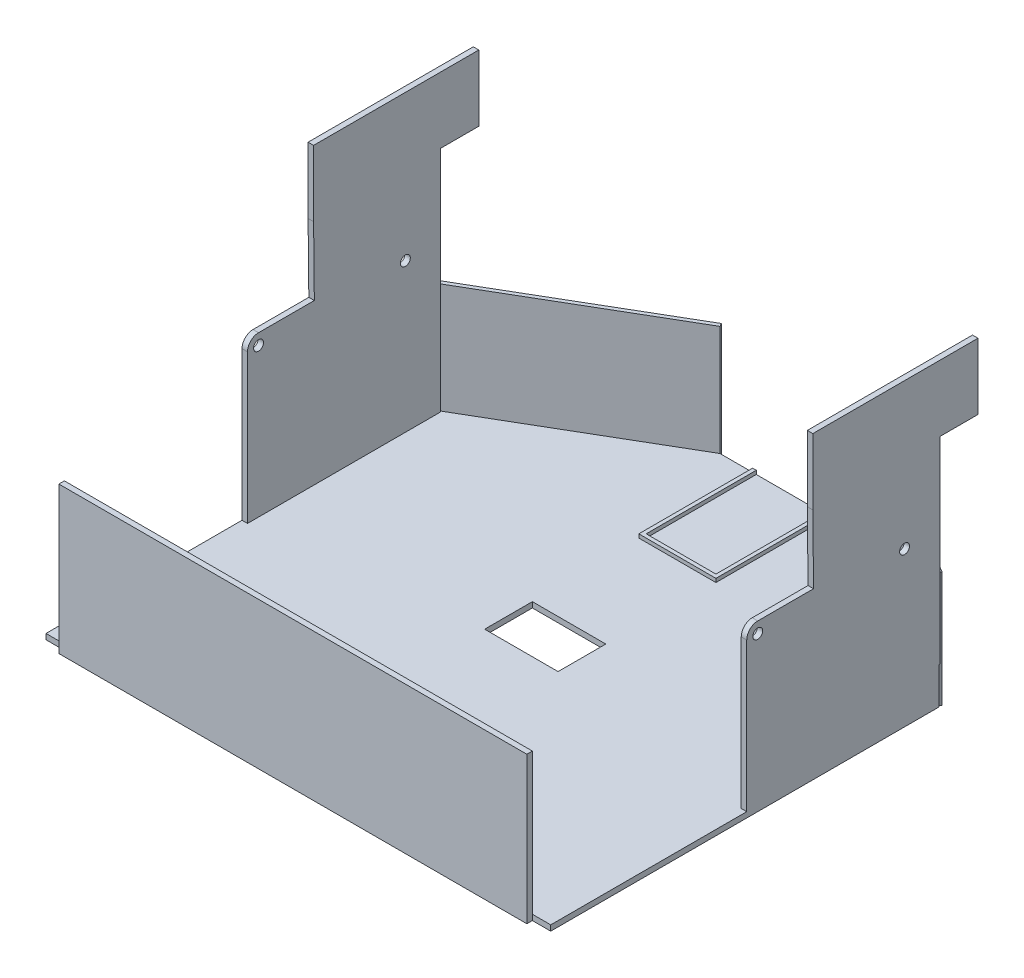
SolidWorks part; units mm, degrees
ref_plane "Front Plane" through (0, 0, 0) normal (0, 0, 1) x (1, 0, 0)
ref_plane "Top Plane" through (0, 0, 0) normal (0, 1, 0) x (1, 0, 0)
ref_plane "Right Plane" through (0, 0, 0) normal (1, 0, 0) x (0, 0, -1)
sketch "Sketch1" plane through (0, 0, 0) normal (0, 1, 0) x (1, 0, 0)
  line L0 (-67.25, 67.25) -> (67.25, 67.25)
  line L1 (-67, 67) -> (67, 67)
  line L2 (-67, 67) -> (-67, -67)
  line L3 (-67, -67) -> (67, -67)
  line L4 (67, 67) -> (67, -67)
  line L5 (-67, 67) -> (67, -67) construction
  line L6 (-67, -67) -> (67, 67) construction
  line L7 (67.25, 67.25) -> (67.25, -67.25)
  line L8 (-67.25, -67.25) -> (67.25, -67.25)
  line L9 (-67.25, 67.25) -> (-67.25, -67.25)
  line L10 (-68.75, 68.75) -> (-68.75, -68.75)
  line L11 (-68.75, -68.75) -> (68.75, -68.75)
  line L12 (68.75, 68.75) -> (68.75, -68.75)
  line L13 (-68.75, 68.75) -> (68.75, 68.75)
  line L14 (-68.75, 68.75) -> (-67, 67)
  line L15 (67, 67) -> (68.75, 68.75)
  line L17 (-10, 6.5) -> (10, 6.5)
  line L18 (-10, 6.5) -> (-10, -6.5)
  line L19 (-10, -6.5) -> (10, -6.5)
  line L20 (10, 6.5) -> (10, -6.5)
  line L21 (-10, 6.5) -> (10, -6.5) construction
  line L22 (-10, -6.5) -> (10, 6.5) construction
  point P0 (0, 0)
  point P14 (0, 0)
  dimension "D1" = 134
  dimension "D2" = 134
  dimension "D5" = 13
  dimension "D6" = 20
  dimension "D3" = 0.25
  dimension "D4" = 1.5
extrude "Boss-Extrude1" add sketch "Sketch1" along normal blind 1.5 contours L4 L1 L2 L3 L17 L20 L19 L18 | L15 L4 L3 L2 L14 L9 L8 L7 region at (-67.1902, 0, 0) region at (0, 0, -65.105)
extrude "Boss-Extrude2" add sketch "Sketch1<3>" along normal blind 45 contours L15 L7 L8 L9 L14 L10 L11 L12 region at (-67.4445, 0, 0)
sketch "Sketch1<3>" plane through (0, 0, 0) normal (0, 1, 0) x (1, 0, 0) same geometry as "Sketch1"
sketch "Sketch2" plane through (-68.75, 0, 0) normal (-1, 0, 0) x (0, 0, 1)
  line L0 (68.75, 0) -> (68.75, 45) construction
  line L1 (-68.75, 45) -> (68.75, 45) construction
  circle A0 centre (10.85, 42) radius 1.35
  circle A1 centre (-29.15, 42) radius 1.35
  dimension "D1" = 2.7
  dimension "D2" = 2.7
  dimension "D3" = 3
  dimension "D4" = 3
  dimension "D6" = 97.9
  dimension "D5" = 57.9
extrude "Cut-Extrude1" cut sketch "Sketch2" against normal up to surface (137.5 mm away) up to face at (68.75, 22.5, 0)
sketch "Sketch3" plane through (-68.75, 0, 0) normal (-1, 0, 0) x (0, 0, 1)
  line L0 (67.25, 45) -> (67.25, 1.5)
  line L1 (67.25, 1.5) -> (13.85, 1.5)
  line L2 (13.85, 1.5) -> (13.85, 45)
  line L3 (-68.75, 45) -> (68.75, 45) construction
  line L4 (68.75, 45) -> (68.75, 0) construction
  line L5 (73.975, 0) -> (-73.975, 0) construction
  line L6 (67.25, 45) -> (13.85, 45)
  circle A0 centre (10.85, 42) radius 1.35 construction
  dimension "D1" = 1.5
  dimension "D2" = 1.5
  dimension "D3" = 3
extrude "Cut-Extrude2" cut sketch "Sketch3" against normal up to surface (137.5 mm away) up to face at (68.75, 42, 9.5)
sketch "Sketch4" plane through (0, 0, 68.75) normal (0, 0, 1) x (1, 0, 0)
  line L0 (0, 45) -> (0, -44.2687) construction
  line L1 (-68.75, 45) -> (68.75, 45) construction
  line L2 (70, 45) -> (70, 40)
  line L3 (70, 40) -> (-70, 40)
  line L4 (0, 40) -> (0, 45)
  line L5 (-70, 45) -> (70, 45)
  line L6 (75.625, 0) -> (-75.625, 0) construction
  line L7 (-70, 45) -> (-70, 40)
  line M8 (68.75, 45) -> (-68.75, 45)
  dimension "D1" = 40
  dimension "D2" = 70
extrude "Cut-Extrude3" cut sketch "Sketch4" against normal up to surface (1.5 mm away) contours L4 L3 L2 M8 | L7 L3 L4 M8 region at (35, 42.5, 68.75) region at (-35, 42.5, 68.75) up to face at (0, 23.25, 67.25)
sketch "Sketch5" plane through (-68.75, 0, 0) normal (-1, 0, 0) x (0, 0, 1)
  line L0 (-68.75, 45) -> (-38.75, 45)
  line L1 (-68.75, 45) -> (13.85, 45) construction
  line L2 (-38.75, 45) -> (-38.75, 1.5)
  line L4 (-38.75, 1.5) -> (-68.75, 1.5)
  line L5 (-68.75, 45) -> (-68.75, 0) construction
  line L6 (-68.75, 1.5) -> (-68.75, 45)
  line L7 (-68.75, 0) -> (68.75, 0) construction
  dimension "D1" = 1.5
  dimension "D2" = 30
extrude "Cut-Extrude4" cut sketch "Sketch5" against normal up to surface (137.5 mm away) up to face at (68.75, 42, 9.5)
sketch "Sketch6" plane through (0, 0, 0) normal (0, -1, 0) x (-1, 0, 0)
  line L0 (68.75, 38.5) -> (19.3866, 67)
  line L1 (68.75, 68.75) -> (68.75, -68.75) construction
  line L2 (67, 67) -> (-67, 67) construction
  line L3 (19.3866, 67) -> (68.75, 67)
  line L4 (68.75, 67) -> (68.75, 38.5)
  line L5 (0, 0) -> (0, 116.2768) construction
  line L6 (-19.3866, 67) -> (-68.75, 67)
  line L7 (-68.75, 38.5) -> (-19.3866, 67)
  line L8 (-68.75, 67) -> (-68.75, 38.5)
  line L9 (67, 67) -> (68.75, 68.75)
  line L10 (68.75, 68.75) -> (68.75, 67)
  line L11 (-68.75, 68.75) -> (-68.75, 67)
  line L12 (-67, 67) -> (-68.75, 68.75)
  line M7 (-67, 67) -> (-68.75, 68.75)
  line M8 (-68.75, 68.75) -> (-68.75, -68.75)
  line M10 (68.75, -68.75) -> (68.75, 68.75)
  line M11 (68.75, 68.75) -> (67, 67)
  line M12 (67, 67) -> (-67, 67)
  dimension "D1" = 28.5
  dimension "D2" = 60
extrude "Cut-Extrude5" cut sketch "Sketch6" against normal blind 10 contours L3 M11 M10 | L3 L0 M12 M10 | L7 L6 M8 M12 | L6 M7 M8 region at (52.2955, 0, -57.5) region at (-52.2955, 0, -57.5) region at (-68.1667, 0, -67.5833) region at (68.1667, 0, -67.5833)
sketch3d "3DSketch1"
  point P0 (-68.75, 9.0262, -10.9608)
ref_plane "Plane1" through (-68.75, 0, 0) normal (-1, 0, 0) x (0, 0, -1)
sketch "Sketch7" plane through (-68.75, 0, 0) normal (-1, 0, 0) x (0, 0, -1)
  line L0 (29.15, -42) -> (29.15, -63.7) construction
  line L1 (29.15, -63.7) -> (4.15, -63.7)
  line L2 (4.15, -63.7) -> (4.15, -81.7)
  line L3 (4.15, -81.7) -> (49.15, -81.7)
  line L4 (49.15, -81.7) -> (49.15, -63.7)
  line L5 (49.15, -63.7) -> (29.15, -63.7)
  line L6 (38.75, -45) -> (38.75, -63.7)
  line L7 (19.55, -45) -> (19.55, -63.7)
  line L8 (19.55, -45) -> (38.75, -45)
  dimension "D1" = 21.7
  dimension "D2" = 18
  dimension "D3" = 25
  dimension "D4" = 20
extrude "Boss-Extrude3" add sketch "Sketch7" against normal up to surface (1.5 mm away) separate body contours L0 L8 L7 L1 | L8 L0 L5 L6 | L4 L5 L1 L2 L3 region at (-68.75, 54.35, -33.95) region at (-68.75, 54.35, -24.35) region at (-68.75, 72.7, -26.65) up to face at (-67.25, 23.25, -12.45)
mirror "Mirror6" about plane through (0, 0, 0) normal (1, 0, 0) of "Boss-Extrude3"
combine bodies "Combine1" operation type add bodies to combine 108 109
sketch "Sketch8" plane through (0, 1.5, 0) normal (0, 1, 0) x (1, 0, 0)
  line L0 (0, 0) -> (0, 67) construction
  line L1 (-19.3866, 67) -> (19.3866, 67) construction
  line L2 (9.5, 67) -> (9.5, 37)
  line L3 (9.5, 37) -> (0, 37)
  line L4 (10.5, 67) -> (10.5, 36)
  line L5 (10.5, 36) -> (0, 36)
  line L6 (10.5, 67) -> (9.5, 67)
  line L7 (0, 36) -> (0, 37)
  line L8 (-10.5, 67) -> (-9.5, 67)
  line L9 (-9.5, 37) -> (0, 37)
  line L10 (-10.5, 36) -> (0, 36)
  line L11 (-9.5, 67) -> (-9.5, 37)
  line L12 (-10.5, 67) -> (-10.5, 36)
  line M12 (19.3866, 67) -> (-19.3866, 67)
  dimension "D1" = 9.5
  dimension "D2" = 30
  dimension "D3" = 1
extrude "Boss-Extrude4" add sketch "Sketch8" along normal blind 1 contours L12 L10 L7 L9 L11 M12 | L7 L5 L4 L2 L3 M12 region at (10, 1.5, -66.6727) region at (-9.8273, 1.5, -52)
sketch "Sketch9" plane through (0, 1.5, 0) normal (0, 1, 0) x (1, 0, 0)
  line L0 (-19.3866, 67) -> (-68.25, 38.5)
  line L1 (-19.8904, 67.8638) -> (-68.7538, 39.3638)
  line L2 (-19.8904, 67.8638) -> (-19.3866, 67)
  line L3 (-68.7538, 39.3638) -> (-68.25, 38.5)
  line L4 (0, 0) -> (0, 82.1499) construction
  line L5 (19.8904, 67.8638) -> (68.7538, 39.3638)
  line L6 (19.8904, 67.8638) -> (19.3866, 67)
  line L7 (19.3866, 67) -> (68.25, 38.5)
  line L8 (68.7538, 39.3638) -> (68.25, 38.5)
  dimension "D1" = 1
extrude "Boss-Extrude5" add sketch "Sketch9" along normal blind 30 and the other way up to surface (1.5 mm away) other way up to face at (0, 0, 0)
sketch "Sketch10" plane through (68.75, 0, 0) normal (1, 0, 0) x (0, 0, -1)
  line L0 (-13.85, 42) -> (-13.85, 45)
  line L1 (-13.85, 45) -> (-10.85, 45)
  arc A0 (-10.85, 45) -> (-13.85, 42) centre (-10.85, 42) ccw
extrude "Cut-Extrude6" cut sketch "Sketch10" against normal up to surface (137.5 mm away) up to face at (-68.75, 38.2, -0.0312)
sketch "Sketch11" plane through (0, 0, 68.75) normal (0, 0, 1) x (1, 0, 0)
  line L0 (0, 40) -> (0, -4.1468)
  line L1 (68.75, 40) -> (-68.75, 40) construction
  line L2 (-68.75, 40) -> (-63.75, 40)
  line L3 (68.75, 0) -> (63.75, 0)
  line L4 (68.75, 0) -> (68.75, 40)
  line L5 (68.75, 40) -> (63.75, 40)
  line L6 (63.75, 0) -> (63.75, 40)
  line L7 (-63.75, 0) -> (-63.75, 40)
  line L8 (-68.75, 0) -> (-63.75, 0)
  line L9 (-68.75, 0) -> (-68.75, 40)
  line M6 (68.75, 40) -> (-68.75, 40)
  line M7 (-68.75, 40) -> (-68.75, 0)
  line M8 (-68.75, 0) -> (68.75, 0)
  line M9 (68.75, 0) -> (68.75, 40)
  dimension "D1" = 5
extrude "Cut-Extrude7" cut sketch "Sketch11" against normal up to surface (1.5 mm away) contours L6 M8 M9 M6 | L7 M8 M6 M7 region at (66.25, 20, 68.75) region at (-66.25, 20, 68.75) up to face at (0, 20.75, 67.25)
sketch "Sketch12" plane through (68.75, 0, 0) normal (1, 0, 0) x (0, 0, -1)
  line L0 (4.15, 63.7) -> (4.35, 45)
  line L1 (19.55, 45) -> (-10.85, 45) construction
  line L2 (4.35, 45) -> (19.55, 45)
  line L3 (19.55, 45) -> (19.55, 63.7)
  line L4 (19.55, 63.7) -> (4.15, 63.7)
extrude "Boss-Extrude6" add sketch "Sketch12" against normal up to surface (1.5 mm away) separate body up to face at (67.25, 42, 9.5)
mirror "Mirror8" about plane through (0, 0, 0) normal (1, 0, 0) of bodies 115
combine bodies "Combine2" operation type add bodies to combine 115 116 114
